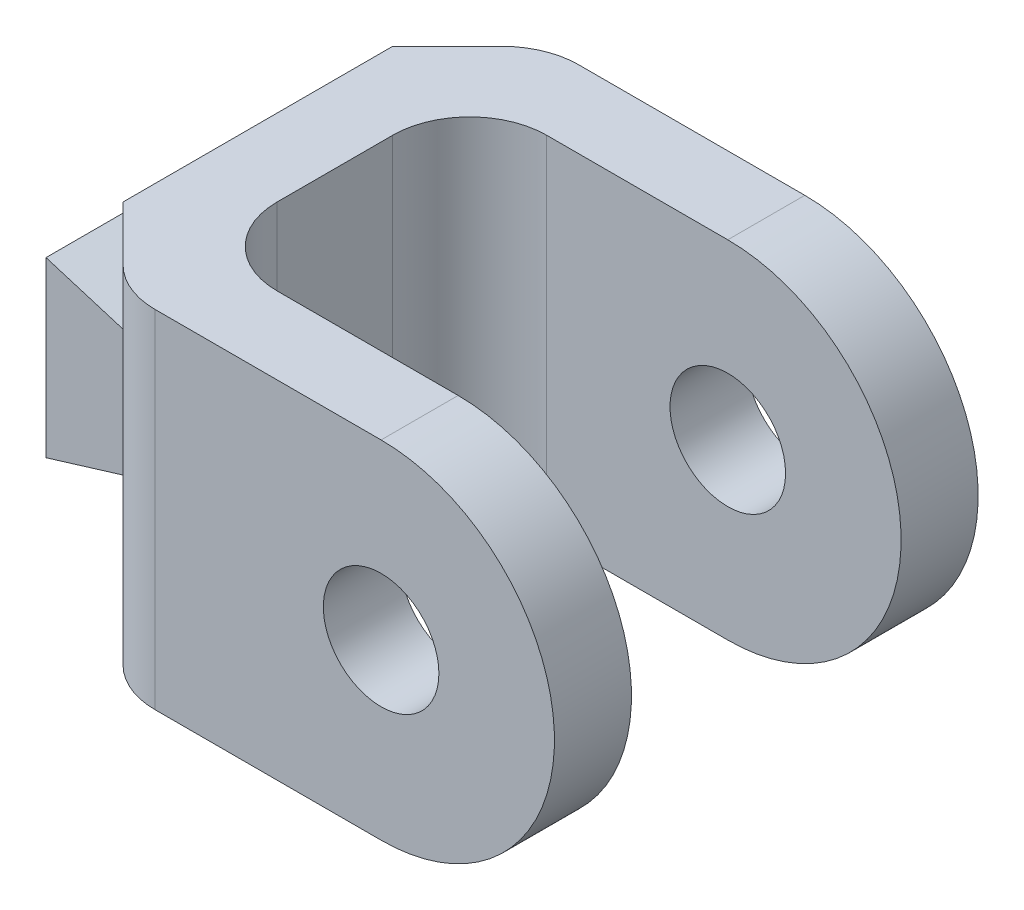
SolidWorks part; units mm, degrees
ref_plane "Front Plane" through (0, 0, 0) normal (0, 0, 1) x (1, 0, 0)
ref_plane "Top Plane" through (0, 0, 0) normal (0, 1, 0) x (1, 0, 0)
ref_plane "Right Plane" through (0, 0, 0) normal (1, 0, 0) x (0, 0, -1)
sketch "Sketch1" plane through (0, 0, 0) normal (0, 0, 1) x (1, 0, 0)
  line L0 (-7.1268, 0) -> (0, 0) construction
  line L1 (0, -4.5) -> (0, -1.64) construction
  line L2 (0, -1.64) -> (-2, -2.25)
  line L6 (-2, -2.25) -> (-2, 2.25)
  line L7 (0, 0) -> (-2, 2.25) construction
  line L8 (0, 0) -> (-2, -2.25) construction
  line L9 (0, 1.64) -> (-2, 2.25)
  line L11 (0, 0) -> (6.5352, 0) construction
  line L12 (0, 1.64) -> (0, 4.5)
  line L13 (0, -4.5) -> (2, -4.5)
  line L14 (0, -4.5) -> (0, -1.64)
  line L15 (0, 4.5) -> (2, 4.5)
  line L16 (2, -4.5) -> (2, 4.5)
  line L17 (0, 1.64) -> (0, 4.499) construction
  point P5 (0, 0)
  point P10 (0, 1.64)
  point P12 (0, -1.64)
  dimension "D1" = 2
  dimension "D2" = 4.5
  dimension "D3" = 9
  dimension "D4" = 4.5
extrude "Boss-Extrude2" add sketch "Sketch1" along normal blind 7
sketch "Sketch2" plane through (0, 0, 0) normal (0, 0, 1) x (1, 0, 0)
  line L1 (0, 4.5) -> (8.7, 4.5)
  line L2 (0, 4.5) -> (0, -4.5)
  line L3 (0, -4.5) -> (8.7, -4.5)
  arc A0 (8.7, -4.5) -> (8.7, 4.5) centre (8.7, 0) ccw
  circle A1 centre (8.7, 0) radius 1.5
  dimension "D3" = 3
extrude "Boss-Extrude3" add sketch "Sketch2" against normal blind 2
ref_plane "Plane1" through (0, 4.5, 0) normal (0, 1, 0) x (1, 0, 0)
sketch "Sketch4" plane through (0, 4.5, 0) normal (0, 1, 0) x (1, 0, 0)
  line L0 (2, 0) -> (2, 2.9724) construction
  line L1 (8.7, 2) -> (0, 2) construction
  line L2 (0, 0) -> (2, 2)
  line L3 (2, 2) -> (0, 2)
  line L4 (0, 0) -> (0, 2)
  point P0 (2, 0)
  point P4 (2, 2)
extrude "Cut-Extrude3" cut sketch "Sketch4" against normal through all
fillet "Fillet1" radius 2 1 edges at (2, 0, 0)
fillet "Fillet2" radius 2 1 edges at (2, 0, -2)
ref_plane "Plane2" through (0, 0, 3.5) normal (0, 0, 1) x (1, 0, 0)
mirror "Mirror2" about plane through (0, 0, 3.5) normal (0, 0, 1) of "Boss-Extrude2", "Fillet2", "Cut-Extrude3", "Boss-Extrude3"
fillet "Fillet3" radius 2 1 edges at (2, 0, 7)
